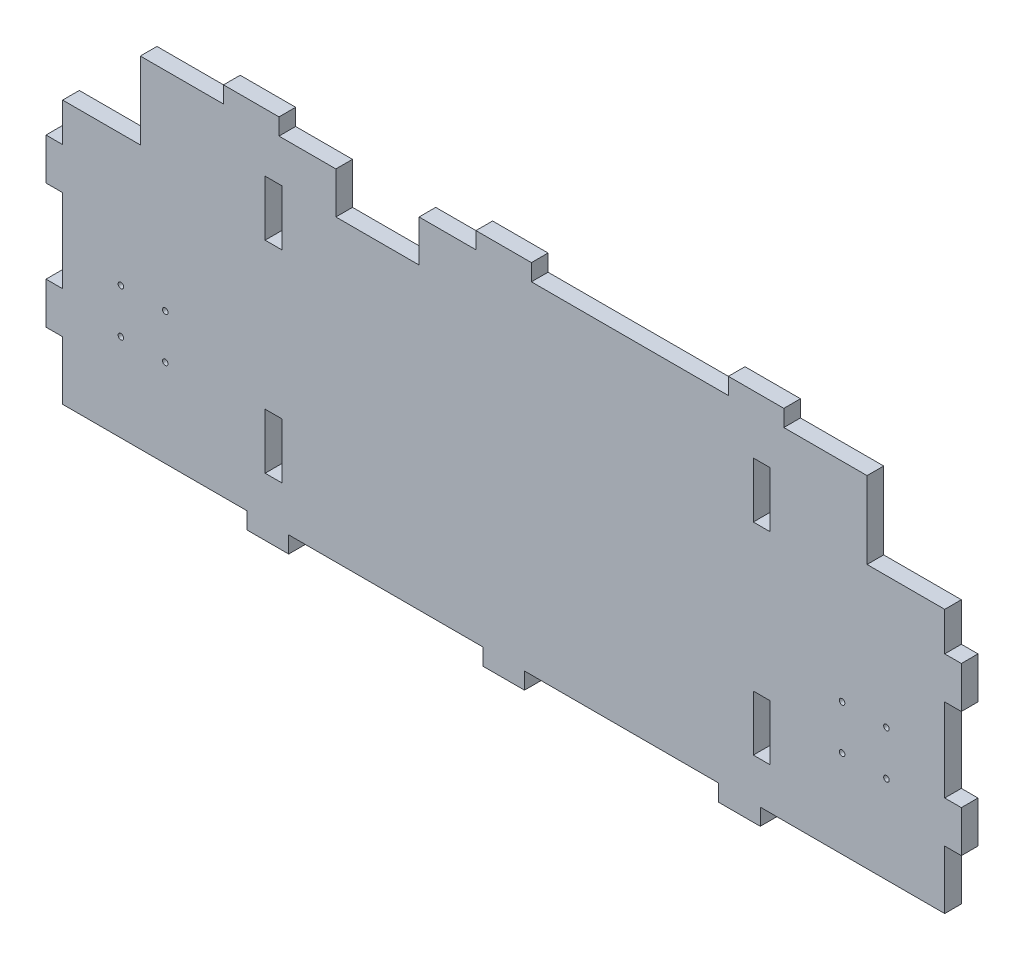
SolidWorks part; units mm, degrees
ref_plane "Plan de face" through (0, 0, 0) normal (0, 0, 1) x (1, 0, 0)
ref_plane "Plan de dessus" through (0, 0, 0) normal (0, 1, 0) x (1, 0, 0)
ref_plane "Plan de droite" through (0, 0, 0) normal (1, 0, 0) x (0, 0, -1)
sketch "Esquisse1" plane through (0, 0, 0) normal (0, 0, 1) x (1, 0, 0)
  line L0 (-159, 35) -> (-131, 35)
  line L1 (0, 102.0551) -> (0, -193.4247) construction
  line L2 (-159, 35) -> (-159, -60)
  line L3 (-159, -60) -> (159, -60)
  line L4 (159, 35) -> (159, -60)
  line L6 (131, 35) -> (131, 62.75)
  line L7 (131, 62.75) -> (-131, 62.75)
  line L8 (-131, 35) -> (-131, 62.75)
  line L9 (159, 35) -> (131, 35)
  line L10 (96, 47.75) -> (90, 47.75)
  line L11 (96, 47.75) -> (96, 27.75)
  line L12 (96, 27.75) -> (90, 27.75)
  line L13 (90, 47.75) -> (90, 27.75)
  line L14 (96, -25.01) -> (90, -25.01)
  line L15 (96, -25.01) -> (96, -45.01)
  line L16 (96, -45.01) -> (90, -45.01)
  line L17 (90, -25.01) -> (90, -45.01)
  line L18 (-80, 47.75) -> (-86, 47.75)
  line L19 (-80, 47.75) -> (-80, 27.75)
  line L20 (-80, 27.75) -> (-86, 27.75)
  line L21 (-86, 47.75) -> (-86, 27.75)
  line L22 (-80, -25.01) -> (-86, -25.01)
  line L23 (-80, -25.01) -> (-80, -45.01)
  line L24 (-80, -45.01) -> (-86, -45.01)
  line L25 (-86, -25.01) -> (-86, -45.01)
  dimension "D1" = 95
  dimension "D2" = 28
  dimension "D3" = 28
  dimension "D4" = 95
  dimension "D6" = 262
  dimension "D7" = 122.75
  dimension "D5" = 159
  dimension "D8" = 318
  dimension "D9" = 6
  dimension "D10" = 20
  dimension "D11" = 20
  dimension "D12" = 6
  dimension "D13" = 6
  dimension "D14" = 20
  dimension "D15" = 6
  dimension "D16" = 20
  dimension "D17" = 52.76
  dimension "D18" = 63
  dimension "D19" = 73
  dimension "D20" = 73
  dimension "D21" = 52.76
  dimension "D22" = 15
  dimension "D23" = 15
  dimension "D24" = 63
extrude "Boss.-Extru.1" add sketch "Esquisse1" along normal blind 6
sketch "Esquisse2" plane through (0, 0, 6) normal (0, 0, 1) x (1, 0, 0)
  line L0 (-159, -60) -> (159, -60) construction
  line L1 (-92.5, -60) -> (-77.5, -60)
  line L2 (-92.5, -60) -> (-92.5, -66)
  line L3 (-92.5, -66) -> (-77.5, -66)
  line L4 (-77.5, -60) -> (-77.5, -66)
  line L5 (-159, 35) -> (-159, -60) construction
  line L6 (-7.5, -60) -> (7.5, -60)
  line L7 (-7.5, -60) -> (-7.5, -66)
  line L8 (-7.5, -66) -> (7.5, -66)
  line L9 (7.5, -60) -> (7.5, -66)
  line L10 (77.5, -60) -> (92.5, -60)
  line L11 (77.5, -60) -> (77.5, -66)
  line L12 (77.5, -66) -> (92.5, -66)
  line L13 (92.5, -60) -> (92.5, -66)
  line L14 (176.2958, 0) -> (-249.7093, -3.2925) construction
  line L15 (0, 107.6082) -> (0, -117.4775) construction
  line L16 (-131, 35) -> (-159, 35) construction
  line L17 (-159, 21.09) -> (-165, 21.09)
  line L18 (-159, 21.09) -> (-159, 6.09)
  line L19 (-159, 6.09) -> (-165, 6.09)
  line L20 (-165, 21.09) -> (-165, 6.09)
  line L21 (-159, -23.91) -> (-165, -23.91)
  line L22 (-159, -23.91) -> (-159, -38.91)
  line L23 (-159, -38.91) -> (-165, -38.91)
  line L24 (-165, -23.91) -> (-165, -38.91)
  line L25 (165, -23.91) -> (165, -38.91)
  line L26 (159, -38.91) -> (165, -38.91)
  line L27 (159, -23.91) -> (159, -38.91)
  line L28 (159, -23.91) -> (165, -23.91)
  line L29 (165, 21.09) -> (165, 6.09)
  line L30 (159, 6.09) -> (165, 6.09)
  line L31 (159, 21.09) -> (159, 6.09)
  line L32 (159, 21.09) -> (165, 21.09)
  line L33 (131, 62.75) -> (-131, 62.75) construction
  line L34 (101, 62.75) -> (81, 62.75)
  line L35 (101, 62.75) -> (101, 68.75)
  line L36 (101, 68.75) -> (81, 68.75)
  line L37 (81, 62.75) -> (81, 68.75)
  line L38 (-131, 62.75) -> (-131, 35) construction
  line L39 (-81, 62.75) -> (-101, 62.75)
  line L40 (-81, 62.75) -> (-81, 68.75)
  line L41 (-81, 68.75) -> (-101, 68.75)
  line L42 (-101, 62.75) -> (-101, 68.75)
  line L43 (10, 62.75) -> (-10, 62.75)
  line L44 (10, 62.75) -> (10, 68.75)
  line L45 (10, 68.75) -> (-10, 68.75)
  line L46 (-10, 62.75) -> (-10, 68.75)
  line L47 (131, 35) -> (131, 62.75) construction
  dimension "D1" = 66.5
  dimension "D2" = 70
  dimension "D3" = 15
  dimension "D4" = 15
  dimension "D5" = 70
  dimension "D6" = 15
  dimension "D7" = 6
  dimension "D8" = 6
  dimension "D9" = 6
  dimension "D10" = 6
  dimension "D11" = 13.91
  dimension "D12" = 15
  dimension "D13" = 30
  dimension "D14" = 15
  dimension "D15" = 20
  dimension "D16" = 20
  dimension "D17" = 20
  dimension "D18" = 30
  dimension "D19" = 30
  dimension "D20" = 121
  dimension "D21" = 6
  dimension "D22" = 6
  dimension "D23" = 6
  dimension "D24" = 6
extrude "Boss.-Extru.2" add sketch "Esquisse2" against normal blind 6
sketch "Esquisse3" plane through (0, 0, 0) normal (0, 0, -1) x (-1, 0, 0)
  line L0 (159, -60) -> (92.5, -60) construction
  line L1 (159, 6.09) -> (159, -23.91) construction
  line L2 (0, 141.59) -> (0, -167.3887) construction
  circle A0 centre (138, -28.38) radius 1
  circle A1 centre (138, -12.38) radius 1
  circle A2 centre (122, -12.38) radius 1
  circle A3 centre (122, -28.38) radius 1
  circle A4 centre (-122, -28.38) radius 1
  circle A5 centre (-122, -12.38) radius 1
  circle A6 centre (-138, -12.38) radius 1
  circle A7 centre (-138, -28.38) radius 1
  dimension "D1" = 31.62
  dimension "D2" = 21
  dimension "D7" = 2
  dimension "D8" = 2
  dimension "D9" = 2
  dimension "D10" = 2
  dimension "D3" = 16
  dimension "D4" = 16
  dimension "D5" = 16
  dimension "D6" = 16
extrude "Enlèv. mat.-Extru.1" cut sketch "Esquisse3" against normal blind 6
sketch "Esquisse4" plane through (0, 0, 0) normal (0, 0, -1) x (-1, 0, 0)
  line L0 (10, 62.75) -> (81, 62.75) construction
  line L1 (30.5, 62.75) -> (60.5, 62.75)
  line L2 (30.5, 62.75) -> (30.5, 47.75)
  line L3 (30.5, 47.75) -> (60.5, 47.75)
  line L4 (60.5, 62.75) -> (60.5, 47.75)
  line L5 (10, 68.75) -> (10, 62.75) construction
  dimension "D1" = 20.5
  dimension "D2" = 30
  dimension "D3" = 15
extrude "Enlèv. mat.-Extru.2" cut sketch "Esquisse4" against normal blind 6
equation "\"D5@Esquisse1\"=\"D8@Esquisse1\"/2"
